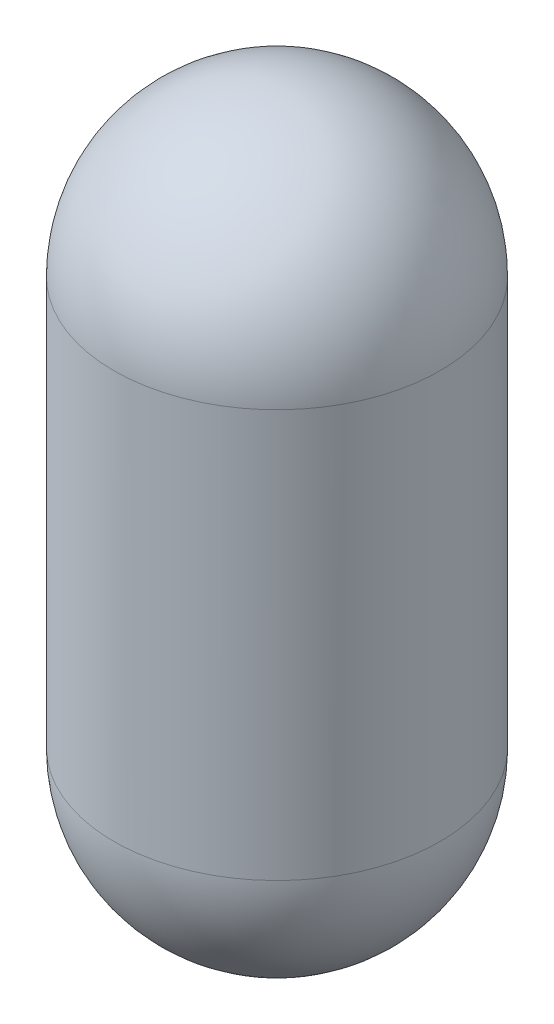
SolidWorks part; units mm, degrees
ref_plane "Front Plane" through (0, 0, 0) normal (0, 0, 1) x (1, 0, 0)
ref_plane "Top Plane" through (0, 0, 0) normal (0, 1, 0) x (1, 0, 0)
ref_plane "Right Plane" through (0, 0, 0) normal (1, 0, 0) x (0, 0, -1)
sketch "Sketch1" plane through (0, 0, 0) normal (0, 1, 0) x (1, 0, 0)
  line L0 (0, 40) -> (0, 35) construction
  line L2 (-2.5, 34.9106) -> (-2.5, -34.9106)
  line L3 (0, 40) -> (0, -40) construction
  line L4 (2.5, 34.9106) -> (2.5, -34.9106)
  circle A0 centre (0, 0) radius 40
  arc A1 (-2.5, 34.9106) -> (-2.5, -34.9106) centre (0, 0) ccw
  arc A2 (2.5, 34.9106) -> (2.5, -34.9106) centre (0, 0) cw
  point P9 (-2.5, 0)
  dimension "D1" = 80
  dimension "D2" = 35
  dimension "D3" = 2.5
extrude "Boss-Extrude1" add sketch "Sketch1" against normal blind 100
sketch "Sketch2" plane through (2.5, 0, 0) normal (1, 0, 0) x (0, 0, -1)
  circle A0 centre (0, -75) radius 15
  dimension "D1" = 30
  dimension "D2" = 75
extrude "Cut-Extrude1" cut sketch "Sketch2" against normal blind 5
sketch "Sketch3" plane through (0, 0, 0) normal (1, 0, 0) x (0, 0, -1)
  line L0 (-34.9106, -100) -> (34.9106, -100) construction
  line L1 (35, -100) -> (40, -100)
  line L2 (0, -140) -> (0, -135)
  arc A0 (40, -100) -> (0, -140) centre (0, -100) cw
  arc A1 (35, -100) -> (0, -135) centre (0, -100) cw
  dimension "D1" = 40
  dimension "D2" = 35
  dimension "D3" = 5
revolve "Revolve1" add sketch "Sketch3" angle 360 about L2
extrude "Boss-Extrude2" add sketch "Sketch1<2>" against normal blind 5 contours L2 A1 | A2 L4 region at (-16.2143, 0, 0) region at (16.2143, 0, 0)
sketch "Sketch1<2>" plane through (0, 0, 0) normal (0, 1, 0) x (1, 0, 0) same geometry as "Sketch1"
sketch "Sketch4" plane through (0, 0, 0) normal (0, 1, 0) x (1, 0, 0)
  circle A0 centre (-15, 0) radius 2.5
  circle A1 centre (15, 0) radius 2.5
  dimension "D1" = 5
  dimension "D2" = 15
  dimension "D3" = 15
extrude "Cut-Extrude2" cut sketch "Sketch4" against normal blind 5
ref_plane "Plane1" through (0, -50, 0) normal (0, 1, 0) x (1, 0, 0)
mirror "Mirror1" about plane through (0, -50, 0) normal (0, 1, 0) of "Revolve1"
